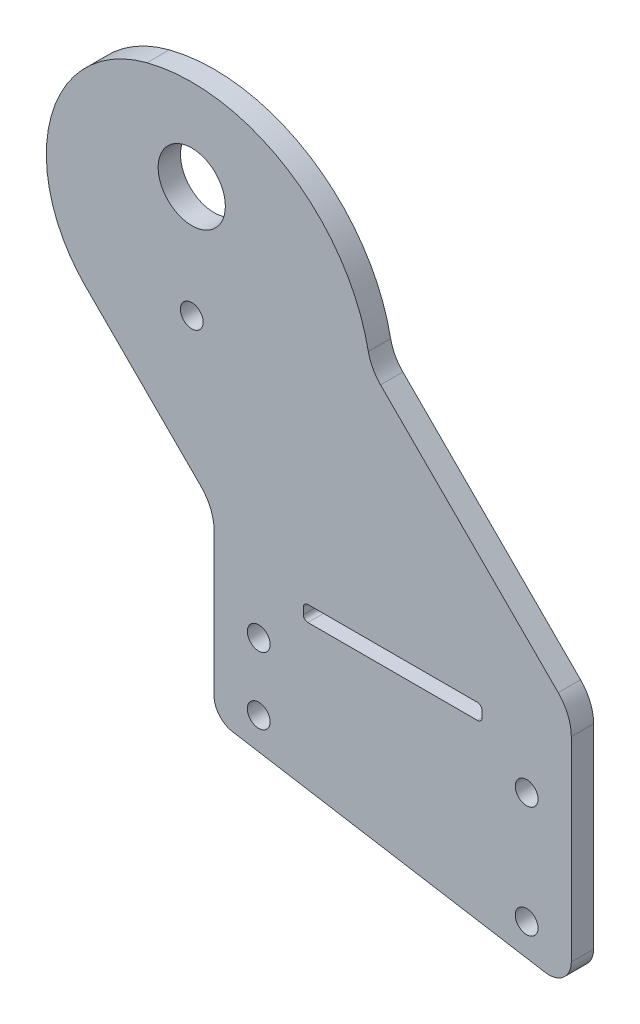
SolidWorks part; units mm, degrees
ref_plane "正面" through (0, 0, 0) normal (0, 0, 1) x (1, 0, 0)
ref_plane "平面" through (0, 0, 0) normal (0, 1, 0) x (1, 0, 0)
ref_plane "右側面" through (0, 0, 0) normal (1, 0, 0) x (0, 0, -1)
sketch "ｽｹｯﾁ1" plane through (0, 0, 0) normal (0, 0, 1) x (1, 0, 0)
  line L0 (-85, -71.4) -> (-85, -11.4) construction
  line L1 (-85, -11.4) -> (-40, 33.6) construction
  line L2 (-40, 33.6) -> (40, 33.6) construction
  line L3 (40, 33.6) -> (85, -11.4)
  line L4 (85, -11.4) -> (85, -71.4)
  line L5 (85, -71.4) -> (-85, -71.4) construction
  line L6 (40, 33.6) -> (-85, -71.4) construction
  line L7 (-40, 33.6) -> (85, -71.4) construction
  line L8 (0, 0) -> (0, -18.9) construction
  line L9 (-75, -61.4) -> (75, -61.4) construction
  line L10 (-75, -61.4) -> (-75, 23.6) construction
  line L11 (-75, 23.6) -> (75, 23.6) construction
  line L12 (75, -61.4) -> (75, 23.6) construction
  line L13 (-75, -61.4) -> (75, 23.6) construction
  line L14 (-75, 23.6) -> (75, -61.4) construction
  line L15 (0, 48.6) -> (0, 0) construction
  line L16 (-40, 33.6) -> (5, -11.4)
  line L17 (5, -11.4) -> (5, -71.4)
  line L18 (5, -71.4) -> (85, -71.4)
  circle A0 centre (75, -31.4) radius 2.55
  circle A1 centre (75, -56.4) radius 2.55
  circle A2 centre (-75, -26.4) radius 2.55 construction
  circle A3 centre (-75, -51.4) radius 2.55 construction
  circle A4 centre (0, 23.6) radius 2.55
  arc A5 (-40, 33.6) -> (40, 33.6) centre (0, 28.6) cw
  circle A6 centre (0, 48.6) radius 7.525
  point P2 (0, 0)
  point P10 (0, -18.9)
  dimension "D9" = 20
  dimension "D13" = 5.1
  dimension "D14" = 5
  dimension "D15" = 15.05
  dimension "D1" = 170
  dimension "D2" = 45
  dimension "D3" = 45
  dimension "D4" = 80
  dimension "D5" = 60
  dimension "D6" = 10
  dimension "D7" = 10
  dimension "D8" = 10
  dimension "D10" = 25
  dimension "D11" = 15
  dimension "D12" = 25
  dimension "D16" = 15
  dimension "D17" = 80
extrude "ﾎﾞｽ - 押し出し1" add sketch "ｽｹｯﾁ1" along normal blind 5
fillet "ﾌｨﾚｯﾄ1" radius 10 3 edges at (85, -11.4, 2.5) (40, 33.6, 2.5) (5, -11.4, 2.5)
sketch "ｽｹｯﾁ2" plane through (0, 0, 5) normal (0, 0, 1) x (1, 0, 0)
  line L0 (15, -71.4) -> (15, -10.4721) construction
  line L1 (5, -71.4) -> (85, -71.4) construction
  line L2 (5, -15.5421) -> (5, -71.4) construction
  line L3 (75, -31.4) -> (15, -31.4) construction
  line L4 (5, -71.4) -> (85, -71.4) construction
  circle A0 centre (15, -46.4) radius 2.55
  circle A1 centre (15, -31.4) radius 2.55
  circle A2 centre (75, -56.4) radius 2.55 construction
  point P11 (0, 0)
  point P16 (0, 0)
  point P17 (0, 0)
  point P18 (0, 0)
  point P19 (17.8737, -56.4)
  point P20 (0, 0)
  dimension "D2" = 25
  dimension "D1" = 10
extrude "ｶｯﾄ - 押し出し1" cut sketch "ｽｹｯﾁ2" against normal through all
fillet "ﾌｨﾚｯﾄ2" radius 30 1 edges at (-40, 33.6, 2.5)
sketch "ｽｹｯﾁ3" plane through (0, 0, 0) normal (0, 0, -1) x (-1, 0, 0)
  line L0 (-45, -71.4) -> (-45, -21.4) construction
  line L1 (-65, -19.9) -> (-25, -19.9)
  line L2 (-65, -19.9) -> (-65, -22.9)
  line L3 (-65, -22.9) -> (-25, -22.9)
  line L4 (-25, -19.9) -> (-25, -22.9)
  line L5 (-65, -19.9) -> (-25, -22.9) construction
  line L6 (-65, -22.9) -> (-25, -19.9) construction
  line L7 (-5, -71.4) -> (-85, -71.4) construction
  point P0 (-45, -21.4)
  dimension "D1" = 3
  dimension "D2" = 40
  dimension "D3" = 50
extrude "ｶｯﾄ - 押し出し2" cut sketch "ｽｹｯﾁ3" against normal through all
sketch "ｽｹｯﾁ5" plane through (0, 0, 0) normal (0, 0, -1) x (-1, 0, 0)
  line L0 (-25, -22.9) -> (-25, -19.9) construction
  line L1 (-65, -19.9) -> (-25, -19.9)
  line L2 (-65, -19.9) -> (-65, -19.4)
  line L3 (-65, -19.4) -> (-25, -19.4)
  line L4 (-25, -19.9) -> (-25, -19.4)
  dimension "D1" = 0.5
extrude "ｶｯﾄ - 押し出し4" cut sketch "ｽｹｯﾁ5" against normal through all
fillet "ﾌｨﾚｯﾄ3" radius 1 4 edges at (65, -19.4, 2.5) (65, -22.9, 2.5) (25, -22.9, 2.5) (25, -19.4, 2.5)
sketch "ｽｹｯﾁ6" plane through (0, 0, 0) normal (0, 0, -1) x (-1, 0, 0)
  line L0 (-5, -51.8299) -> (-122.4207, -71.4)
  line L1 (-5, -15.5421) -> (-5, -71.4) construction
  line L2 (-5, -71.4) -> (-85, -71.4) construction
  line L3 (-122.4207, -71.4) -> (-5, -71.4)
  line L4 (-5, -71.4) -> (-5, -51.8299)
  line L5 (-15, -46.4) -> (-75, -56.4) construction
  dimension "D1" = 7
extrude "ｶｯﾄ - 押し出し5" cut sketch "ｽｹｯﾁ6" against normal through all
fillet "ﾌｨﾚｯﾄ4" radius 5 2 edges at (85, -65.1632, 2.5) (5, -51.8299, 2.5)
